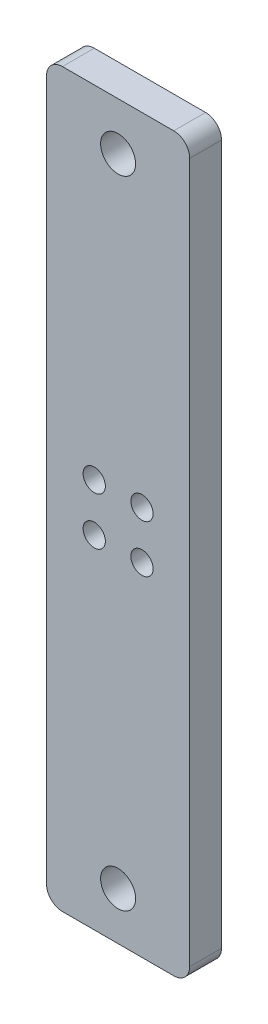
SolidWorks part; units mm, degrees
material "1.0038 (S235JRG2)"
ref_plane "Ön Düzlem" through (0, 0, 0) normal (0, 0, 1) x (1, 0, 0)
ref_plane "Üst Düzlem" through (0, 0, 0) normal (0, 1, 0) x (1, 0, 0)
ref_plane "Sağ Düzlem" through (0, 0, 0) normal (1, 0, 0) x (0, 0, -1)
sketch "Çizim1" plane through (0, 0, 0) normal (0, 0, 1) x (1, 0, 0)
  line L1 (-22.5, 115) -> (22.5, 115)
  line L2 (-22.5, 115) -> (-22.5, -115)
  line L3 (-22.5, -115) -> (22.5, -115)
  line L4 (22.5, 115) -> (22.5, -115)
  line L5 (-22.5, 115) -> (22.5, -115) construction
  line L6 (-22.5, -115) -> (22.5, 115) construction
  point P0 (0, 0)
  dimension "D1" = 230
  dimension "D2" = 45
base flange "Taban-Flanş1" sketch "Çizim1" thickness 10 reverse thickness direction no parameters "D1"=2
sketch "Çizim6" plane through (0, 0, 0) normal (0, 0, 1) x (1, 0, 0)
  line L1 (-7.5, 7.5) -> (7.5, 7.5) construction
  line L2 (-7.5, 7.5) -> (-7.5, -7.5) construction
  line L3 (-7.5, -7.5) -> (7.5, -7.5) construction
  line L4 (7.5, 7.5) -> (7.5, -7.5) construction
  line L5 (-7.5, 7.5) -> (7.5, -7.5) construction
  line L6 (-7.5, -7.5) -> (7.5, 7.5) construction
  circle A0 centre (7.5, 7.5) radius 3.5
  circle A1 centre (-7.5, 7.5) radius 3.5
  circle A2 centre (7.5, -7.5) radius 3.5
  circle A3 centre (-7.5, -7.5) radius 3.5
  point P0 (0, 0)
  dimension "D1" = 7
  dimension "D2" = 15
  dimension "D3" = 15
extrude "Kes-Ekstrüzyon1" cut sketch "Çizim6" against normal blind 26
sketch "Çizim7" plane through (0, 0, 0) normal (0, 0, 1) x (1, 0, 0)
  circle A0 centre (0, -100) radius 5.5
  circle A1 centre (0, 100) radius 5.5
  dimension "D1" = 11
  dimension "D3" = 100
  dimension "D2" = 100
extrude "Kes-Ekstrüzyon2" cut sketch "Çizim7" against normal blind 10
fillet "Radyus1" radius 5 4 edges at (22.5, 115, -5) (-22.5, 115, -5) (22.5, -115, -5) (-22.5, -115, -5)
sketch "Büküm-Çizgileri1" [suppressed] plane through (0, 0, 0) normal (0, 1, 0) x (1, 0, 0)
sketch "Sınırlandırma-Kutusu1" [suppressed] plane through (0, 0, 0) normal (0, 1, 0) x (1, 0, 0)
sheet metal parameters "Sac-Levha1" thickness 10 parameters "D1"=2
flat pattern "Düz-Çoğaltma1" [suppressed]
sketch "Büküm-Çizgileri2" plane through (0, 0, 0) normal (0, 1, 0) x (1, 0, 0)
sketch3d "Sınırlandırma-Kutusu2" [suppressed]
  line L0 (-50, 75, 0) -> (-50, -75, 0) construction
  line L1 (50, 75, 0) -> (50, -75, 0) construction
  line L2 (-50, 75, 0) -> (50, 75, 0) construction
  line L3 (-50, -75, 0) -> (50, -75, 0) construction
sheet metal parameters "Sac-Levha2" thickness 10 parameters "D1"=2
flat pattern "Düz-Çoğaltma1"
sketch "Büküm-Çizgileri2" plane through (0, 0, 0) normal (0, 1, 0) x (1, 0, 0)
sketch3d "Sınırlandırma-Kutusu2" [suppressed]
  line L0 (27.5, 75, 0) -> (27.5, -75, 0) construction
  line L1 (-27.5, 75, 0) -> (-27.5, -75, 0) construction
  line L2 (27.5, 75, 0) -> (-27.5, 75, 0) construction
  line L3 (27.5, -75, 0) -> (-27.5, -75, 0) construction
sheet metal parameters "Sac-Levha3" thickness 10 parameters "D1"=2
flat pattern "Düz-Çoğaltma1"
sketch "Büküm-Çizgileri2" plane through (0, 0, 0) normal (0, 1, 0) x (1, 0, 0)
sketch3d "Sınırlandırma-Kutusu2" [suppressed]
  line L0 (22.5, -115, 0) -> (22.5, 115, 0) construction
  line L1 (-22.5, -115, 0) -> (-22.5, 115, 0) construction
  line L2 (22.5, -115, 0) -> (-22.5, -115, 0) construction
  line L3 (22.5, 115, 0) -> (-22.5, 115, 0) construction
